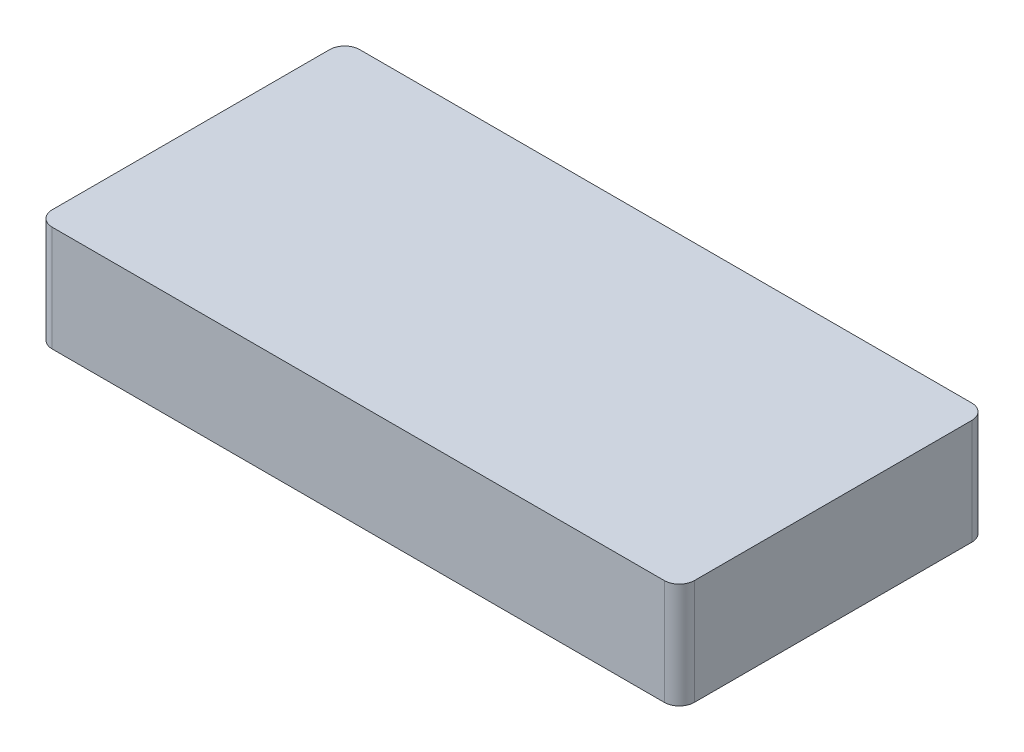
SolidWorks part; units mm, degrees
ref_plane "Front Plane" through (0, 0, 0) normal (0, 0, 1) x (1, 0, 0)
ref_plane "Top Plane" through (0, 0, 0) normal (0, 1, 0) x (1, 0, 0)
ref_plane "Right Plane" through (0, 0, 0) normal (1, 0, 0) x (0, 0, -1)
sketch "Sketch1" plane through (0, 0, 0) normal (0, 1, 0) x (1, 0, 0)
  line L1 (-27.051, -12.954) -> (27.051, -12.954)
  line L2 (-27.051, -12.954) -> (-27.051, 12.954)
  line L3 (-27.051, 12.954) -> (27.051, 12.954)
  line L4 (27.051, -12.954) -> (27.051, 12.954)
  line L5 (-27.051, -12.954) -> (27.051, 12.954) construction
  line L6 (-27.051, 12.954) -> (27.051, -12.954) construction
  point P0 (0, 0)
  dimension "D1" = 54.102
  dimension "D2" = 25.908
extrude "Boss-Extrude1" add sketch "Sketch1" along normal blind 8.89
fillet "Fillet1" radius 1.27 4 edges at (-27.051, 4.445, -12.954) (-27.051, 4.445, 12.954) (27.051, 4.445, -12.954) (27.051, 4.445, 12.954)
